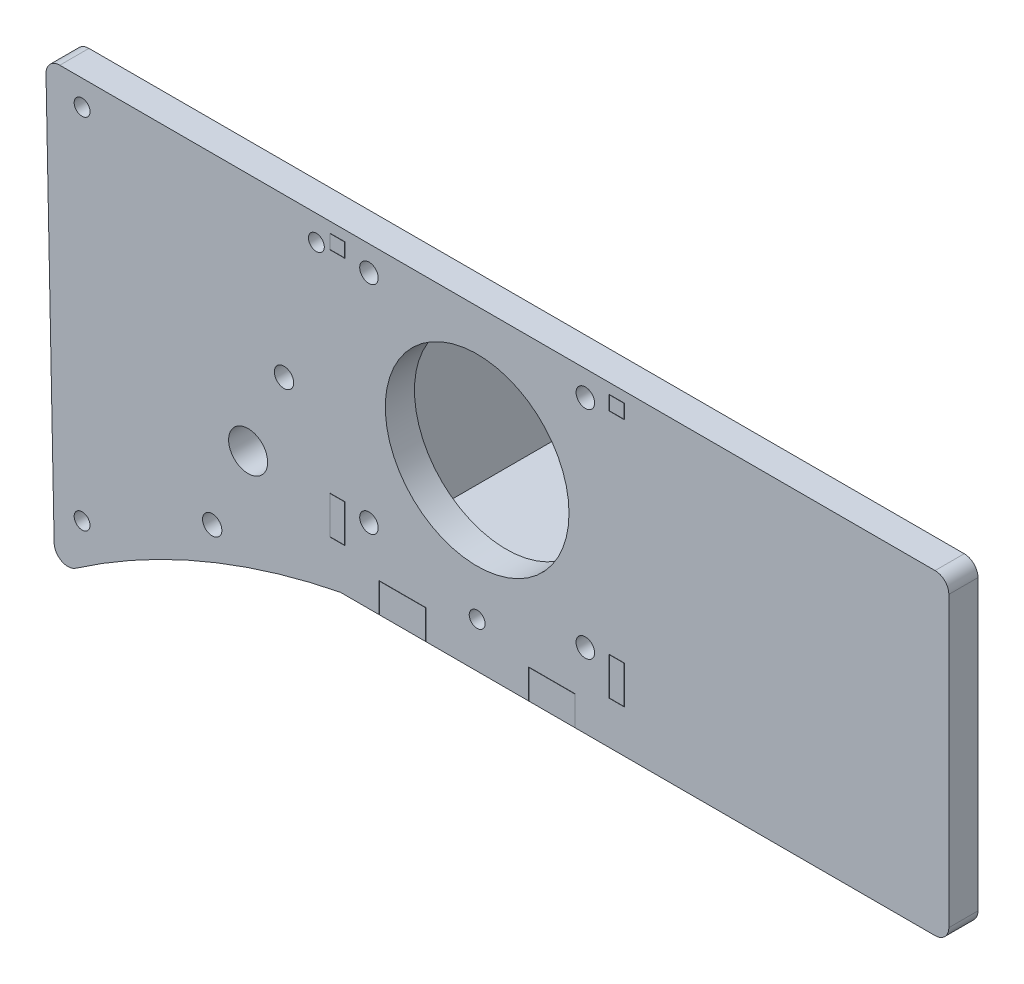
SolidWorks part; units mm, degrees
material "6061 Alloy"
ref_plane "Front Plane" through (0, 0, 0) normal (0, 0, 1) x (1, 0, 0)
ref_plane "Top Plane" through (0, 0, 0) normal (0, 1, 0) x (1, 0, 0)
ref_plane "Right Plane" through (0, 0, 0) normal (1, 0, 0) x (0, 0, -1)
ref_axis "Axis1" through (0, -55, 0) along (0, 1, 0)
sketch "Sketch1" plane through (0, 0, 0) normal (0, 0, 1) x (1, 0, 0)
  line L0 (-23.55, 23.55) -> (-23.55, -23.55) construction
  line L1 (-23.55, -23.55) -> (23.55, -23.55) construction
  line L2 (23.55, -23.55) -> (23.55, 23.55) construction
  line L3 (23.55, 23.55) -> (-23.55, 23.55) construction
  line L4 (0, 0) -> (0, -17.6837) construction
  line L6 (-93.9196, 29.0263) -> (-91.9679, -67.3528)
  line L7 (0, -53.0085) -> (0, 53.0085) construction
  line L10 (32.829, -40.4307) -> (32.829, 26.0263)
  line L11 (29.829, 29.0263) -> (-93.9196, 29.0263)
  line L12 (0, 0) -> (-49.8611, 0) construction
  line L13 (-49.8611, 0) -> (-49.8611, -23.2136) construction
  line L14 (-49.8611, -23.2136) -> (0, 0) construction
  circle A1 centre (-49.8611, -23.2136) radius 4.2488
  circle A2 centre (0, 0) radius 6
  arc A5 (32.829, 26.0263) -> (29.829, 29.0263) centre (29.829, 26.0263) ccw
  arc A7 (32.829, -40.4307) -> (-91.9679, -67.3528) centre (0, -190.96) ccw
  circle A8 centre (-23.55, 23.55) radius 2.0195
  circle A9 centre (-23.55, -23.55) radius 2.0195
  circle A10 centre (23.55, -23.55) radius 2.0195
  circle A11 centre (23.55, 23.55) radius 2.0195
  point P26 (0, 0)
  dimension "D1" = 4.039
  dimension "D2" = 47.1
  dimension "D3" = 47.1
  dimension "D10" = 1.16
  dimension "D7" = 23.55
  dimension "D11" = 29.0263
  dimension "D15" = 40.4307
  dimension "D13" = 96.3791
  dimension "D6" = 12
  dimension "D9" = 154.0676
  dimension "D12" = 3
  dimension "D16" = 8.4977
  dimension "D4" = 23.55
  dimension "D5" = 93.3127
  dimension "D8" = 32.829
  dimension "D17" = 55
  dimension "D18" = 23.2136
extrude "10-32" add sketch "Sketch1" along normal blind 6.35
sketch "Sketch2" plane through (0, 0, 6.35) normal (0, 0, 1) x (1, 0, 0)
  circle A0 centre (0, 0) radius 20
  dimension "D1" = 40
extrude "Cut-Extrude1" cut sketch "Sketch2" against normal blind 6.35
sketch "Sketch4" plane through (0, 0, 0) normal (0, 0, -1) x (-1, 0, 0)
  line L0 (42.0469, -5.4057) -> (57.6754, -41.0214) construction
  line L1 (0, -55) -> (0, 55) construction
  circle A1 centre (42.0469, -5.4057) radius 2.1
  circle A3 centre (57.6754, -41.0214) radius 2.1
  circle A5 centre (49.8611, -23.2136) radius 4.2488 construction
  dimension "D1" = 4.2
  dimension "D3" = 57.6754
  dimension "D2" = 38.8938
  dimension "D4" = 23.2136
  dimension "D5" = 49.8611
extrude "M5" cut sketch "Sketch4" against normal blind 6.35
fillet "Fillet2" radius 3 3 edges at (32.829, -40.4307, 3.175) (-91.9679, -67.3528, 3.175) (-93.9196, 29.0263, 3.175)
sketch "Sketch5" plane through (0, 0, 6.35) normal (0, 0, 1) x (1, 0, 0)
  line L0 (23.55, 23.55) -> (-125.3112, 23.55) construction
  line L1 (-86, 30.944) -> (-86, 56.6744) construction
  circle A0 centre (-86, 23.55) radius 1.727
  circle A1 centre (-86, -54.45) radius 1.727
  circle A2 centre (-35, 23.55) radius 1.727
  circle A3 centre (0, -30) radius 1.727
  dimension "D1" = 3.454
  dimension "D2" = 51
  dimension "D3" = 78
  dimension "D4" = 30
  dimension "D5" = 86
extrude "8-32" cut sketch "Sketch5" against normal blind 10
sketch "Sketch6" plane through (0, 0, 0) normal (0, 0, -1) x (-1, 0, 0)
  line L0 (33.9877, -39.8) -> (33.9877, -33.1658)
  line L1 (-45, -39.8) -> (-102.679, -39.8)
  line L2 (-102.679, -39.8) -> (-102.679, 29.0263)
  line L3 (-29.829, 29.0263) -> (90.8582, 29.0263) construction
  line L4 (-102.679, 29.0263) -> (-29.829, 29.0263)
  line L6 (-45, -45.38) -> (45, -45.38)
  line L7 (45, -45.38) -> (45, -39.8)
  line L8 (45, -39.8) -> (-45, -39.8)
  line L9 (-45, -39.8) -> (-45, -45.38)
  line L12 (33.9877, -39.8) -> (-45, -39.8)
  line L15 (33.9877, -33.1658) -> (-30.1123, -33.1658)
  line L16 (-30.1123, -33.1658) -> (-29.829, 29.0263)
  line L17 (-32.829, -36.7508) -> (-32.829, 26.0263) construction
  dimension "D2" = 69.85
  dimension "D3" = 6.6342
  dimension "D1" = 0
extrude "Boss-Extrude1" add sketch "Sketch6" against normal up to surface (6.35 mm away) up to face at (1.727, -30, 6.35)
sketch "Sketch7" plane through (0, 0, 0) normal (0, 0, -1) x (-1, 0, 0)
  line L0 (45, -39.8) -> (45, -45.38) construction
  line L1 (-45, -39.8) -> (-45, -45.38) construction
  line L2 (-45, -33.45) -> (-45, -39.8)
  line L3 (45, -33.45) -> (45, -39.8)
  line L4 (45, -39.8) -> (-45, -39.8) construction
  line L5 (45, -39.8) -> (-45, -39.8)
  line L6 (45, -33.45) -> (-45, -33.45)
  dimension "D1" = 6.35
extrude "Boss-Extrude2" add sketch "Sketch7" along normal blind 56.175 separate body
sketch "Sketch8" plane through (0, -33.45, 0) normal (0, 1, 0) x (1, 0, 0)
  line L0 (-38, 48.7729) -> (-38, 25.7729) construction
  line L1 (-35.8, 48.7729) -> (-35.8, 25.7729)
  line L2 (-40.2, 48.7729) -> (-40.2, 25.7729)
  line L3 (0, 56.0065) -> (0, 0) construction
  line L8 (-45, 48.7729) -> (-45, 25.7729)
  line L9 (-45, 56.175) -> (-45, 0) construction
  line L10 (-31, 48.7729) -> (-31, 25.7729) construction
  line L12 (-32, -16.4247) -> (-58.4945, -16.4247)
  line L13 (-58.4945, -16.4247) -> (-58.4945, 89.1103)
  line L15 (-32, 22.1673) -> (-32, -16.4247)
  line L21 (-45, 56.175) -> (45, 56.175) construction
  line L24 (38, 48.7729) -> (38, 25.7729) construction
  line L25 (-32, 52.3784) -> (32, 52.3784)
  line L27 (0, 81.6227) -> (0, 52.3784) construction
  line L28 (-58.4945, 89.1103) -> (0, 81.6227)
  line L29 (35.8, 48.7729) -> (35.8, 25.7729)
  line L30 (40.2, 48.7729) -> (40.2, 25.7729)
  line L31 (58.4945, 89.1103) -> (0, 81.6227)
  line L32 (32, 22.1673) -> (32, -16.4247)
  line L33 (58.4945, -16.4247) -> (58.4945, 89.1103)
  line L34 (32, -16.4247) -> (58.4945, -16.4247)
  line L35 (45, 48.7729) -> (45, 25.7729)
  circle A0 centre (-38, 45.7729) radius 1.65 construction
  arc A1 (35.8, 48.7729) -> (40.2, 48.7729) centre (38, 48.7729) cw
  circle A2 centre (-38, 45.7729) radius 1.65 construction
  circle A4 centre (-38, 29.7729) radius 1.65 construction
  arc A5 (40.2, 25.7729) -> (35.8, 25.7729) centre (38, 25.7729) cw
  circle A6 centre (-38, 29.7729) radius 1.65 construction
  arc A8 (-35.8, 48.7729) -> (-40.2, 48.7729) centre (-38, 48.7729) ccw
  arc A9 (-40.2, 25.7729) -> (-35.8, 25.7729) centre (-38, 25.7729) ccw
  circle A12 centre (38, 29.7729) radius 1.65 construction
  circle A13 centre (38, 45.7729) radius 1.65 construction
  arc A14 (-45, 25.7729) -> (-32, 22.1673) centre (-38, 25.7729) ccw
  arc A15 (-32, 52.3784) -> (-45, 48.7729) centre (-38, 48.7729) ccw
  arc A16 (-45, 25.7729) -> (-31, 25.7729) centre (-38, 25.7729) ccw construction
  arc A17 (-31, 48.7729) -> (-45, 48.7729) centre (-38, 48.7729) ccw construction
  arc A18 (32, 52.3784) -> (45, 48.7729) centre (38, 48.7729) cw
  arc A19 (45, 25.7729) -> (32, 22.1673) centre (38, 25.7729) cw
  point P8 (0, 56.175)
  point P14 (-38, 37.2729)
  point P20 (38, 37.2729)
  dimension "D3" = 2.2
  dimension "D1" = 3
  dimension "D2" = 4
  dimension "D4" = 26.4945
  dimension "D5" = 58.9718
  dimension "D6" = 38.592
  dimension "D7" = 32
  dimension "D8" = 29.2443
extrude "Cut-Extrude2" cut sketch "Sketch8" against normal blind 10
ref_plane "Plane1" through (32, 0, 0) normal (1, 0, 0) x (0, 0, -1)
ref_plane "Plane2" through (-32, 0, 0) normal (-1, 0, 0) x (0, 0, 1)
sketch "Sketch10" plane through (0, 0, 0) normal (1, 0, 0) x (0, 0, -1)
  line L0 (0, -33.45) -> (52.3784, -33.45)
  line L1 (0, -33.45) -> (4, -33.45)
  line L2 (0, 29.0263) -> (0, -39.8) construction
  line L3 (0, 27.6516) -> (0, 26.7034)
  line L4 (51.6899, -32.6288) -> (0.8832, 27.9729)
  line L5 (48.7729, -39.8) -> (25.7729, -39.8) construction
  line L6 (48.7729, -39.8) -> (25.7729, -39.8) construction
  line L7 (12.1534, -33.45) -> (39.1534, -33.45)
  line L8 (4, -39.8) -> (12.1534, -39.8)
  line L9 (4, -39.8) -> (4, -33.45)
  line L11 (12.1534, -39.8) -> (12.1534, -33.45)
  line L12 (39.1534, -39.8) -> (47.3068, -39.8)
  line L13 (39.1534, -39.8) -> (39.1534, -33.45)
  line L15 (47.3068, -39.8) -> (47.3068, -33.45)
  line L16 (47.3068, -33.45) -> (51.3068, -33.45)
  line L17 (-6.35, 25.9655) -> (-6.35, -61.6596) construction
  line L18 (-6.35, 25.9655) -> (-6.35, -61.6596) construction
  line L19 (0, -30.45) -> (0, -33.45)
  line L20 (0, -30.45) -> (-6.35, -30.45)
  line L22 (0, -22.2966) -> (-6.35, -22.2966)
  line L23 (-6.35, -30.45) -> (-6.35, -22.2966)
  line L24 (0, 23.7034) -> (-6.35, 23.7034)
  line L26 (0, 26.7034) -> (-6.35, 26.7034)
  line L27 (-6.35, 23.7034) -> (-6.35, 26.7034)
  line L28 (0, 23.7034) -> (0, -22.2966)
  arc A0 (0, 27.6516) -> (0.8832, 27.9729) centre (0.5, 27.6516) cw
  arc A1 (51.3068, -33.45) -> (51.6899, -32.6288) centre (51.3068, -32.95) ccw
  dimension "D6" = 0.5
  dimension "D7" = 0.5
  dimension "D1" = 3
  dimension "D2" = 4
  dimension "D3" = 27
  dimension "D4" = 46
  dimension "D5" = 3
extrude "Boss-Extrude3" add sketch "Sketch10" against normal blind 3.175 from surface separate body starting at plane "Plane1"
extrude "Boss-Extrude4" add sketch "Sketch10<2>" along normal blind 3.175 from surface separate body starting at plane "Plane2"
sketch "Sketch10<2>" plane through (0, 0, 0) normal (1, 0, 0) x (0, 0, -1) same geometry as "Sketch10"
sketch "Sketch12" plane through (0, 0, 0) normal (0, 0, 1) x (1, 0, 0)
  line L0 (-32, -33.45) -> (32, -33.45) construction
  line L1 (-21.2797, -33.45) -> (-11.2518, -33.45)
  line L2 (-21.2797, -33.45) -> (-21.2797, -39.8)
  line L3 (-21.2797, -39.8) -> (-11.2518, -39.8)
  line L4 (-11.2518, -33.45) -> (-11.2518, -39.8)
  line L5 (32, -39.8) -> (-32, -39.8) construction
  line L6 (0, -34.3888) -> (0, 34.3888) construction
  line L7 (11.2518, -33.45) -> (11.2518, -39.8)
  line L8 (21.2797, -39.8) -> (11.2518, -39.8)
  line L9 (21.2797, -33.45) -> (21.2797, -39.8)
  line L10 (21.2797, -33.45) -> (11.2518, -33.45)
extrude "Boss-Extrude5" add sketch "Sketch12" along normal up to surface (6.35 mm away) up to face at (-30.4125, -26.3733, 6.35)
sketch "Sketch13" plane through (0, 0, 0) normal (0, 0, 1) x (1, 0, 0)
  line L8 (-32.07, 26.7734) -> (-32.07, 23.6334)
  line L9 (-32.07, 23.6334) -> (-28.755, 23.6334)
  line L10 (-28.755, 23.6334) -> (-28.755, 26.7734)
  line L11 (-28.755, 26.7734) -> (-32.07, 26.7734)
  line L12 (-32.07, 26.7734) -> (-32.07, 23.6334)
  line L13 (-32.07, 23.6334) -> (-28.755, 23.6334)
  line L14 (-28.755, 23.6334) -> (-28.755, 26.7734)
  line L15 (-28.755, 26.7734) -> (-32.07, 26.7734)
  line L20 (-32.07, -22.2266) -> (-32.07, -30.52)
  line L21 (-32.07, -30.52) -> (-28.755, -30.52)
  line L22 (-28.755, -30.52) -> (-28.755, -22.2266)
  line L23 (-28.755, -22.2266) -> (-32.07, -22.2266)
  line L24 (-32.07, -22.2266) -> (-32.07, -30.52)
  line L25 (-32.07, -30.52) -> (-28.755, -30.52)
  line L26 (-28.755, -30.52) -> (-28.755, -22.2266)
  line L27 (-28.755, -22.2266) -> (-32.07, -22.2266)
  line L32 (32.07, 23.6334) -> (32.07, 26.7734)
  line L33 (32.07, 26.7734) -> (28.755, 26.7734)
  line L34 (28.755, 26.7734) -> (28.755, 23.6334)
  line L35 (28.755, 23.6334) -> (32.07, 23.6334)
  line L36 (32.07, 23.6334) -> (32.07, 26.7734)
  line L37 (32.07, 26.7734) -> (28.755, 26.7734)
  line L38 (28.755, 26.7734) -> (28.755, 23.6334)
  line L39 (28.755, 23.6334) -> (32.07, 23.6334)
  line L44 (32.07, -30.52) -> (32.07, -22.2266)
  line L45 (32.07, -22.2266) -> (28.755, -22.2266)
  line L46 (28.755, -22.2266) -> (28.755, -30.52)
  line L47 (28.755, -30.52) -> (32.07, -30.52)
  line L48 (32.07, -30.52) -> (32.07, -22.2266)
  line L49 (32.07, -22.2266) -> (28.755, -22.2266)
  line L50 (28.755, -22.2266) -> (28.755, -30.52)
  line L51 (28.755, -30.52) -> (32.07, -30.52)
  line L56 (-11.1818, -33.38) -> (-21.3497, -33.38)
  line L57 (-21.3497, -33.38) -> (-21.3497, -39.87)
  line L58 (-21.3497, -39.87) -> (-11.1818, -39.87)
  line L59 (-11.1818, -39.87) -> (-11.1818, -33.38)
  line L60 (-11.1818, -33.38) -> (-21.3497, -33.38)
  line L61 (-21.3497, -33.38) -> (-21.3497, -39.87)
  line L62 (-21.3497, -39.87) -> (-11.1818, -39.87)
  line L63 (-11.1818, -39.87) -> (-11.1818, -33.38)
  line L68 (21.3497, -39.87) -> (21.3497, -33.38)
  line L69 (21.3497, -33.38) -> (11.1818, -33.38)
  line L70 (11.1818, -33.38) -> (11.1818, -39.87)
  line L71 (11.1818, -39.87) -> (21.3497, -39.87)
  line L72 (21.3497, -39.87) -> (21.3497, -33.38)
  line L73 (21.3497, -33.38) -> (11.1818, -33.38)
  line L74 (11.1818, -33.38) -> (11.1818, -39.87)
  line L75 (11.1818, -39.87) -> (21.3497, -39.87)
  dimension "D1" = 0.07
  dimension "D2" = 0.07
  dimension "D3" = 0.07
  dimension "D4" = 0.07
  dimension "D5" = 0.07
  dimension "D6" = 0.07
extrude "Cut-Extrude5" cut sketch "Sketch13" along normal blind 23.175
sketch "Sketch15" plane through (0, 0, 0) normal (0, 1, 0) x (1, 0, 0)
  line L8 (32.07, 3.93) -> (32.07, 12.2234)
  line L9 (28.755, 3.93) -> (32.07, 3.93)
  line L10 (28.755, 12.2234) -> (28.755, 3.93)
  line L11 (32.07, 12.2234) -> (28.755, 12.2234)
  line L12 (32.07, 3.93) -> (32.07, 12.2234)
  line L13 (28.755, 3.93) -> (32.07, 3.93)
  line L14 (28.755, 12.2234) -> (28.755, 3.93)
  line L15 (32.07, 12.2234) -> (28.755, 12.2234)
  line L20 (32.07, 39.0834) -> (32.07, 47.3768)
  line L21 (28.755, 39.0834) -> (32.07, 39.0834)
  line L22 (28.755, 47.3768) -> (28.755, 39.0834)
  line L23 (32.07, 47.3768) -> (28.755, 47.3768)
  line L24 (32.07, 39.0834) -> (32.07, 47.3768)
  line L25 (28.755, 39.0834) -> (32.07, 39.0834)
  line L26 (28.755, 47.3768) -> (28.755, 39.0834)
  line L27 (32.07, 47.3768) -> (28.755, 47.3768)
  line L32 (-32.07, 47.3768) -> (-32.07, 39.0834)
  line L33 (-28.755, 47.3768) -> (-32.07, 47.3768)
  line L34 (-28.755, 39.0834) -> (-28.755, 47.3768)
  line L35 (-32.07, 39.0834) -> (-28.755, 39.0834)
  line L36 (-32.07, 47.3768) -> (-32.07, 39.0834)
  line L37 (-28.755, 47.3768) -> (-32.07, 47.3768)
  line L38 (-28.755, 39.0834) -> (-28.755, 47.3768)
  line L39 (-32.07, 39.0834) -> (-28.755, 39.0834)
  line L44 (-32.07, 12.2234) -> (-32.07, 3.93)
  line L45 (-28.755, 12.2234) -> (-32.07, 12.2234)
  line L46 (-28.755, 3.93) -> (-28.755, 12.2234)
  line L47 (-32.07, 3.93) -> (-28.755, 3.93)
  line L48 (-32.07, 12.2234) -> (-32.07, 3.93)
  line L49 (-28.755, 12.2234) -> (-32.07, 12.2234)
  line L50 (-28.755, 3.93) -> (-28.755, 12.2234)
  line L51 (-32.07, 3.93) -> (-28.755, 3.93)
  dimension "D1" = 0.07
  dimension "D2" = 0.07
  dimension "D3" = 0.07
  dimension "D4" = 0.07
extrude "Cut-Extrude6" cut sketch "Sketch15" against normal blind 95.175
fillet "Fillet3" radius 3 2 edges at (102.679, -39.8, 3.175) (102.679, 29.0263, 3.175)
sketch "Sketch16" plane through (0, 0, 0) normal (0, 0, -1) x (-1, 0, 0)
  line L1 (-101.0294, -36.8915) -> (-31.1794, -36.8915)
  line L2 (-101.0294, -36.8915) -> (-101.0294, 32.9585)
  line L3 (-101.0294, 32.9585) -> (-31.1794, 32.9585)
  line L4 (-31.1794, -36.8915) -> (-31.1794, 32.9585)
  dimension "D1" = 69.85
  dimension "D2" = 69.85
fillet "Fillet4" radius 6 4 edges at (-32, -36.625, -52.3784) (-32, -36.625, -22.1673) (32, -36.625, -52.3784) (32, -36.625, -22.1673)
